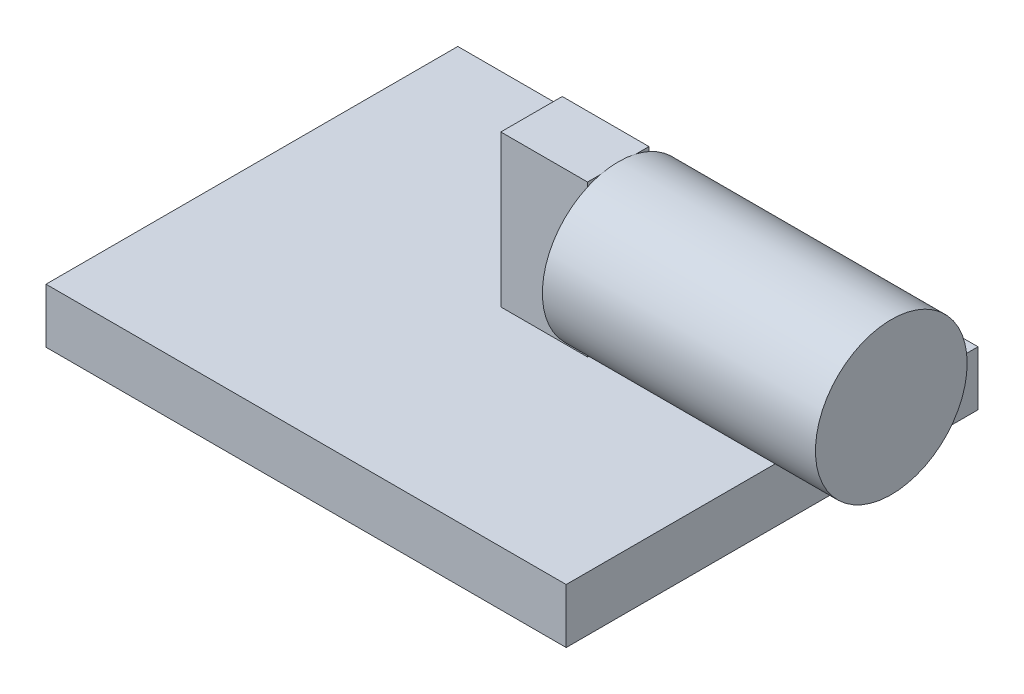
SolidWorks part; units mm, degrees
ref_plane "Front Plane" through (0, 0, 0) normal (0, 0, 1) x (1, 0, 0)
ref_plane "Top Plane" through (0, 0, 0) normal (0, 1, 0) x (1, 0, 0)
ref_plane "Right Plane" through (0, 0, 0) normal (1, 0, 0) x (0, 0, -1)
sketch "Sketch1" plane through (0, 0, 0) normal (0, 1, 0) x (1, 0, 0)
  line L1 (-9.525, -7.5406) -> (9.525, -7.5406)
  line L2 (-9.525, -7.5406) -> (-9.525, 7.5406)
  line L3 (-9.525, 7.5406) -> (9.525, 7.5406)
  line L4 (9.525, -7.5406) -> (9.525, 7.5406)
  line L5 (-9.525, -7.5406) -> (9.525, 7.5406) construction
  line L6 (-9.525, 7.5406) -> (9.525, -7.5406) construction
  point P0 (0, 0)
  dimension "D1" = 15.0813
  dimension "D2" = 19.05
extrude "Board" add sketch "Sketch1" along normal blind 2
ref_plane "Plane1" through (12.7, 0, 0) normal (1, 0, 0) x (0, 0, -1)
sketch "Sketch2" plane through (12.7, 0, 0) normal (1, 0, 0) x (0, 0, -1)
  line L0 (-7.5406, 2) -> (7.5406, 2) construction
  line L1 (7.5406, 2) -> (7.5406, 0) construction
  circle A0 centre (1.1906, 4.85) radius 2.7781
  dimension "D1" = 5.5562
  dimension "D2" = 2.85
  dimension "D3" = 6.35
extrude "LaserBarrel" add sketch "Sketch2" against normal blind 10 separate body
sketch "Sketch4" plane through (2.7, 0, 0) normal (-1, 0, 0) x (0, 0, 1)
  line L0 (-7.5406, 2) -> (7.5406, 2) construction
  line L1 (-2.3156, 7.55) -> (-0.0656, 7.55)
  line L2 (-2.3156, 7.55) -> (-2.3156, 2)
  line L3 (-2.3156, 2) -> (-0.0656, 2)
  line L4 (-0.0656, 7.55) -> (-0.0656, 2)
  line L5 (-1.1906, 7.6281) -> (-1.1906, 2.0719) construction
  circle A0 centre (-1.1906, 4.85) radius 2.7781 construction
  point P11 (-1.1906, 7.55)
  dimension "D1" = 5.55
  dimension "D2" = 2.25
extrude "Boss-Extrude3" add sketch "Sketch4" along normal blind 3.175
